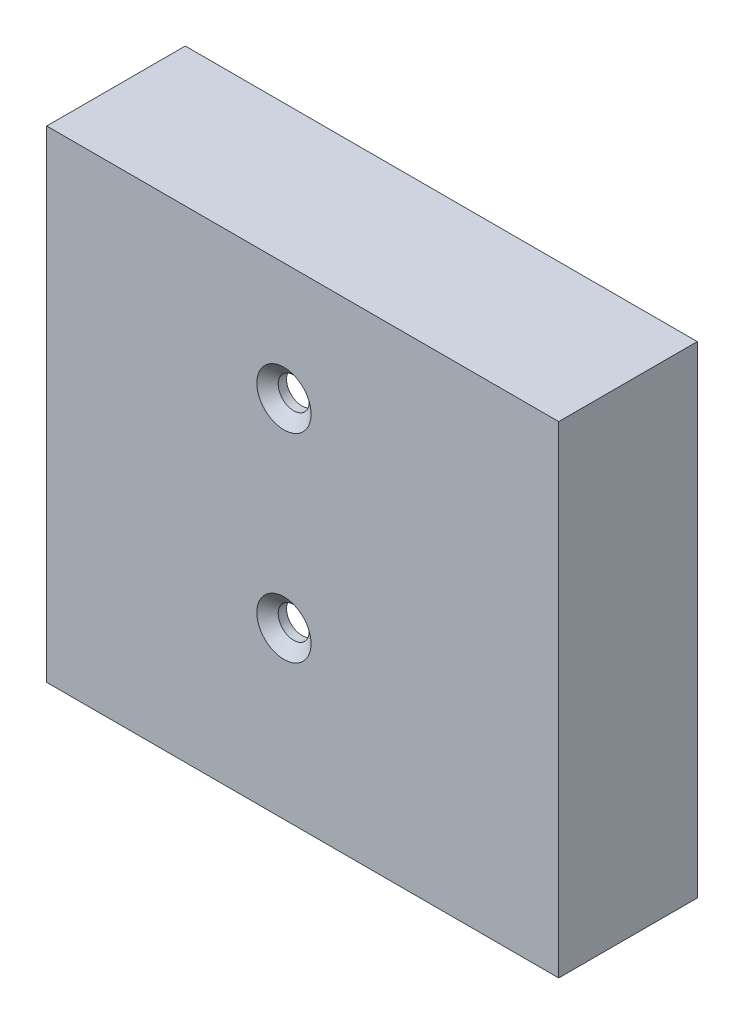
SolidWorks part; units mm, degrees
material "PET"
ref_plane "Front Plane" through (0, 0, 0) normal (0, 0, 1) x (1, 0, 0)
ref_plane "Top Plane" through (0, 0, 0) normal (0, 1, 0) x (1, 0, 0)
ref_plane "Right Plane" through (0, 0, 0) normal (1, 0, 0) x (0, 0, -1)
sketch "Sketch1" plane through (0, 0, 0) normal (0, 0, 1) x (1, 0, 0)
  line L1 (0, 0) -> (52.3875, 0)
  line L2 (0, 0) -> (0, 50.8)
  line L3 (0, 50.8) -> (52.3875, 50.8)
  line L4 (52.3875, 0) -> (52.3875, 50.8)
  dimension "D1" = 50.8
  dimension "D2" = 52.3875
extrude "Boss-Extrude1" add sketch "Sketch1" along normal blind 1.905
sketch "Sketch2" plane through (0, 0, 0) normal (-1, 0, 0) x (0, 0, 1)
  line L1 (1.905, 0) -> (-12.7, 0)
  line L2 (1.905, 0) -> (1.905, 50.8)
  line L3 (1.905, 50.8) -> (-12.7, 50.8)
  line L4 (-12.7, 0) -> (-12.7, 50.8)
  dimension "D1" = 14.605
extrude "Boss-Extrude2" add sketch "Sketch2" along normal blind 1.5875 contours L3 L4 L1 L2
sketch "Sketch3" plane through (0, 0, 0) normal (0, 0, -1) x (-1, 0, 0)
  line L0 (0, 50.8) -> (-52.3875, 50.8)
  line L1 (-52.3875, 50.8) -> (-52.3875, 0)
  line L2 (-52.3875, 0) -> (0, 0)
  line L3 (0, 0) -> (0, 2.54)
  line L4 (0, 50.8) -> (0, 0) construction
  line L5 (0, 2.54) -> (-49.8475, 2.54)
  line L6 (-49.8475, 2.54) -> (-49.8475, 48.26)
  line L7 (-49.8475, 48.26) -> (0, 48.26)
  line L8 (0, 48.26) -> (0, 50.8)
  dimension "D1" = 2.54
  dimension "D2" = 2.54
  dimension "D3" = 2.54
extrude "Boss-Extrude3" add sketch "Sketch3" along normal up to surface (12.7 mm away) up to face at (-0.7937, 25.4, -12.7)
sketch "Sketch4" plane through (0, 0, 0) normal (0, -1, 0) x (1, 0, 0)
  line L0 (17.145, 0) -> (17.145, -15.24) construction
  line L1 (6.985, -12.7) -> (17.145, -12.7)
  line L2 (6.985, -12.7) -> (6.985, -8.8392)
  line L3 (6.985, -8.8392) -> (17.145, -8.8392)
  line L4 (17.145, -12.7) -> (17.145, -8.8392)
  line L5 (-1.5875, -12.7) -> (52.3875, -12.7) construction
  dimension "D1" = 3.8608
extrude "Cut-Extrude1" cut sketch "Sketch4" against normal up to next contours L3 L4 L1 L2
sketch "Sketch5" plane through (0, 0, 0) normal (0, -1, 0) x (1, 0, 0)
  line L0 (0, 0) -> (49.8475, 0) construction
  line L1 (6.985, -12.7) -> (0, -12.7)
  line L2 (6.985, -12.7) -> (6.985, 0)
  line L3 (6.985, 0) -> (0, 0)
  line L4 (0, -12.7) -> (0, 0)
  line L5 (17.145, -12.7) -> (24.257, -12.7)
  line L6 (17.145, -12.7) -> (17.145, 0)
  line L7 (17.145, 0) -> (24.257, 0)
  line L8 (24.257, -12.7) -> (24.257, 0)
  dimension "D1" = 7.112
  dimension "D2" = 6.985
extrude "Cut-Extrude2" cut sketch "Sketch5" against normal up to next
sketch "Sketch6" plane through (0, 0, 0) normal (0, 0, -1) x (-1, 0, 0)
  line L1 (-17.145, 2.54) -> (-6.985, 2.54)
  line L2 (-17.145, 2.54) -> (-17.145, 5.08)
  line L3 (-17.145, 5.08) -> (-6.985, 5.08)
  line L4 (-6.985, 2.54) -> (-6.985, 5.08)
  dimension "D1" = 2.54
extrude "Boss-Extrude4" add sketch "Sketch6" along normal up to surface (8.8392 mm away) up to face at (12.065, 1.27, -8.8392)
sketch "Sketch8" plane through (0, 0, 0) normal (0, 0, -1) x (-1, 0, 0)
  line L1 (0, 48.26) -> (-1.27, 48.26)
  line L2 (0, 48.26) -> (0, 6.858)
  line L3 (0, 6.858) -> (-1.27, 6.858)
  line L4 (-1.27, 48.26) -> (-1.27, 6.858)
  line L5 (-6.985, 0) -> (0, 0) construction
  dimension "D1" = 1.27
  dimension "D2" = 6.858
extrude "Boss-Extrude5" add sketch "Sketch8" along normal offset from surface (14.2875 mm away) 1.5875 contours L4 L3 L2 L1 up to face at (24.9809, 20.32, -12.7) offset beyond the face yes
sketch "Sketch9" plane through (0, 0, -12.7) normal (0, 0, -1) x (-1, 0, 0)
  line L0 (0, 48.26) -> (0, 48.895)
  line L1 (0, 48.895) -> (-50.4825, 48.895)
  line L2 (-50.4825, 48.895) -> (-50.4825, 1.905)
  line L3 (-50.4825, 1.905) -> (-24.257, 1.905)
  line L4 (-24.257, 2.54) -> (-24.257, 0) construction
  line L5 (-24.257, 1.905) -> (-24.257, 2.54)
  line L6 (-24.257, 2.54) -> (-49.8475, 2.54)
  line L7 (-49.8475, 2.54) -> (-49.8475, 48.26)
  line L8 (-49.8475, 48.26) -> (0, 48.26)
  line L9 (1.5875, 50.8) -> (-52.3875, 50.8) construction
  line L10 (-52.3875, 50.8) -> (-52.3875, 0) construction
  line L11 (-24.257, 0) -> (-52.3875, 0) construction
  dimension "D1" = 1.905
  dimension "D2" = 1.905
  dimension "D3" = 1.905
extrude "Boss-Extrude6" add sketch "Sketch9" along normal up to surface (1.5875 mm away) up to face at (0.635, 27.559, -14.2875)
sketch "Sketch11" plane through (1.27, 0, 0) normal (1, 0, 0) x (0, 0, -1)
  line L0 (12.7, 48.895) -> (12.7, 1.905) construction
  line L1 (14.2875, 27.94) -> (12.7, 27.94)
  line L2 (14.2875, 27.94) -> (14.2875, 22.86)
  line L3 (14.2875, 22.86) -> (12.7, 22.86)
  line L4 (12.7, 27.94) -> (12.7, 22.86)
  line L5 (12.7, 14.605) -> (14.2875, 14.605)
  line L6 (12.7, 14.605) -> (12.7, 9.525)
  line L7 (12.7, 9.525) -> (14.2875, 9.525)
  line L8 (14.2875, 14.605) -> (14.2875, 9.525)
  line L9 (14.2875, 48.895) -> (14.2875, 1.905) construction
  line L10 (14.2875, 1.905) -> (12.7, 1.905) construction
  line L11 (12.7, 48.895) -> (14.2875, 48.895)
  line L12 (12.7, 48.895) -> (12.7, 43.815)
  line L13 (12.7, 43.815) -> (14.2875, 43.815)
  line L14 (14.2875, 48.895) -> (14.2875, 43.815)
  line L15 (14.2875, 48.26) -> (14.2875, 6.858) construction
  line L16 (14.2875, 48.895) -> (14.2875, 6.858) construction
  line L17 (-1.905, 50.8) -> (12.7, 50.8) construction
  dimension "D1" = 5.08
  dimension "D2" = 5.08
  dimension "D3" = 5.08
  dimension "D4" = 7.62
  dimension "D5" = 22.86
extrude "Cut-Extrude3" cut sketch "Sketch11" against normal up to next
sketch "Sketch12" plane through (0, 0, 1.905) normal (0, 0, 1) x (1, 0, 0)
  point P0 (23.4188, 17.4625)
  point P1 (23.4188, 38.4175)
hole_wizard "CSK for #4 Flat Head Machine Screw (100)1" positions "Sketch15" profile "Sketch16" countersink size "#4" standard "ANSI Inch"
sketch "Sketch15" plane through (0, 0, 1.905) normal (0, 0, 1) x (1, 0, 0)
  point P0 (23.4188, 38.4175)
  point P3 (23.4188, 17.4625)
sketch "Sketch16" plane through (23.4188, 38.4175, 1.905) normal (1, 0, 0) x (0, -1, 0)
  line L0 (0, 0) -> (0, 8.4736)
  line L1 (0, 8.4736) -> (1.6319, 7.493)
  line L2 (1.6319, 7.493) -> (1.6319, 1.0284)
  line L3 (1.6319, 1.0284) -> (2.8575, 0)
  line L5 (2.8575, 0) -> (0, 0)
  line L6 (-1.6319, 1.0284) -> (-2.8575, 0) construction
  line L10 (0, 8.4736) -> (-1.632, 7.493) construction
  line L11 (0, -6.35) -> (0, 107.95) construction
  dimension "Hole Dia." = 3.2639
  dimension "Hole Depth" = 7.493
  dimension "Near C'Sink Dia." = 5.715
  dimension "Near C'Sink Angle" = 100
  dimension "Drill Angle" = 118
